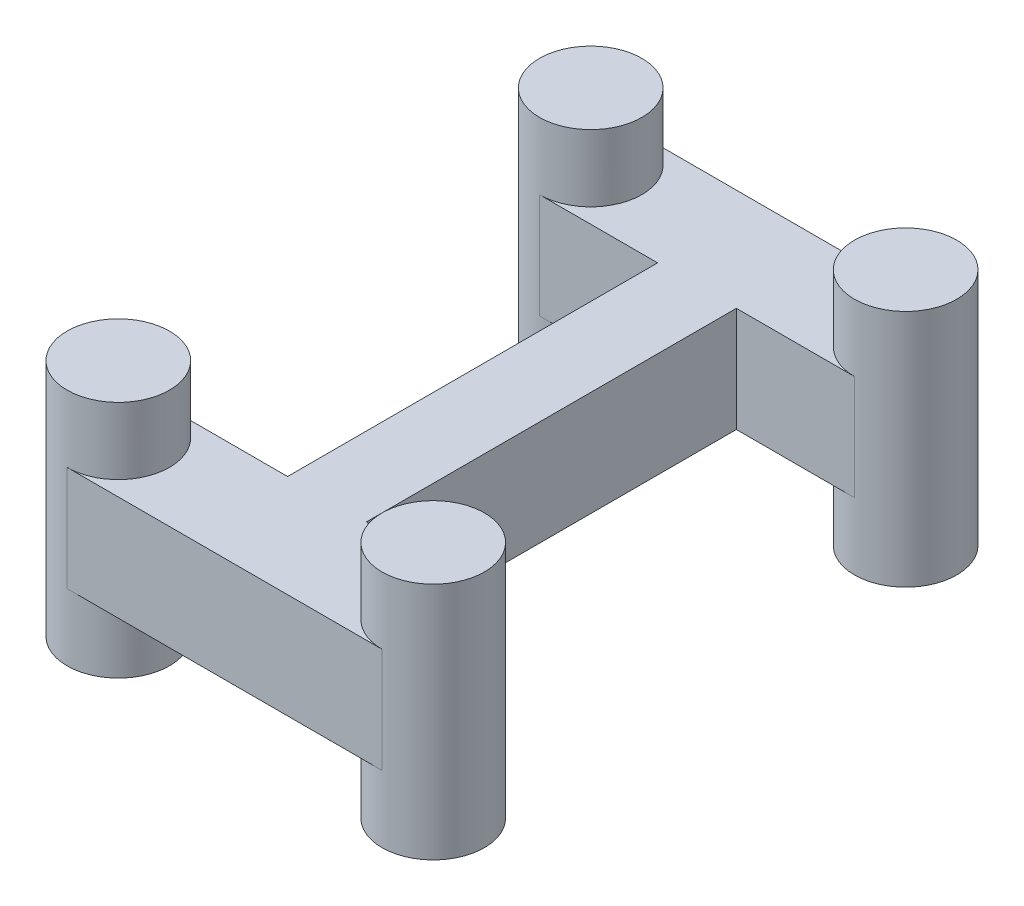
SolidWorks part; units mm, degrees
ref_plane "Front Plane" through (0, 0, 0) normal (0, 0, 1) x (1, 0, 0)
ref_plane "Top Plane" through (0, 0, 0) normal (0, 1, 0) x (1, 0, 0)
ref_plane "Right Plane" through (0, 0, 0) normal (1, 0, 0) x (0, 0, -1)
sketch "Sketch1" plane through (0, 0, 0) normal (0, 1, 0) x (1, 0, 0)
  line L0 (0, -10.95) -> (0, 10.95) construction
  line L1 (-6, -9) -> (6, -9) construction
  line L2 (-6, -9) -> (-6, 9) construction
  line L3 (-6, 9) -> (6, 9) construction
  line L4 (6, -9) -> (6, 9) construction
  line L5 (-6, -9) -> (6, 9) construction
  line L6 (-6, 9) -> (6, -9) construction
  line L7 (-6, -10.95) -> (6, -10.95)
  line L8 (6, -7.05) -> (1.5, -7.05)
  line L9 (-1.5, 7.05) -> (-1.5, -7.05)
  line L10 (-6, 7.05) -> (-1.5, 7.05)
  line L12 (6, 10.95) -> (-6, 10.95)
  line L13 (1.5, -7.05) -> (1.5, 7.05)
  line L14 (1.5, 7.05) -> (6, 7.05)
  line L15 (-1.5, -7.05) -> (-6, -7.05)
  circle A0 centre (-6, 9) radius 1.95
  circle A1 centre (6, 9) radius 1.95
  circle A2 centre (6, -9) radius 1.95
  circle A3 centre (-6, -9) radius 1.95
  point P0 (0, 0)
  point P24 (0, 0)
  dimension "D3" = 3.9
  dimension "D4" = 3.9
  dimension "D5" = 3.9
  dimension "D6" = 3.9
  dimension "D1" = 18
  dimension "D2" = 12
  dimension "D7" = 1.5
  dimension "D8" = 1.5
extrude "Boss-Extrude1" add sketch "Sketch1" along normal blind 2 and the other way blind 2 contours A3 L7 A2 L8 L13 L14 A1 L12 A0 L10 L9 L15 region at (0, 0, 0)
extrude "Boss-Extrude2" add sketch "Sketch1<4>" along normal blind 4.55 and the other way blind 4.55 contours A0 | A1 | A3 | A2 region at (-6, 0, 9) region at (6, 0, 9) region at (-6, 0, -9) region at (6, 0, -9)
sketch "Sketch1<4>" plane through (0, 0, 0) normal (0, 1, 0) x (1, 0, 0) same geometry as "Sketch1"
equation "\"2.5.00mm\"=10"
